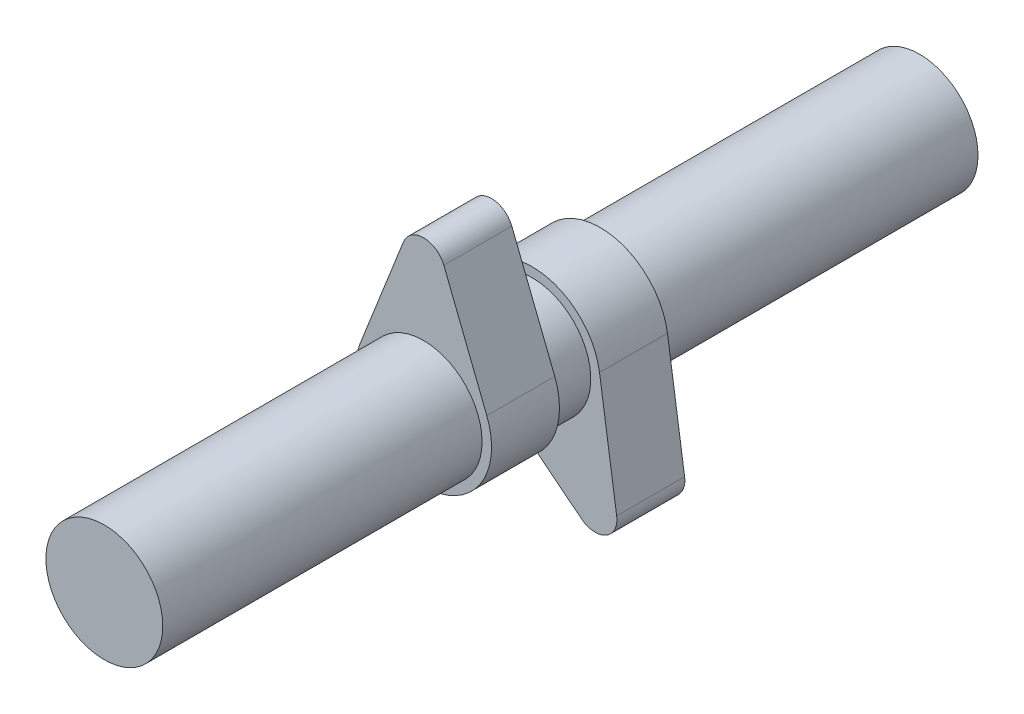
SolidWorks part; units mm, degrees
ref_plane "Front Plane" through (0, 0, 0) normal (0, 0, 1) x (1, 0, 0)
ref_plane "Top Plane" through (0, 0, 0) normal (0, 1, 0) x (1, 0, 0)
ref_plane "Right Plane" through (0, 0, 0) normal (1, 0, 0) x (0, 0, -1)
sketch "Sketch2" plane through (0, 0, 0) normal (0, 0, 1) x (1, 0, 0)
  circle A0 centre (0, 0) radius 21.5
  dimension "D1" = 43
extrude "Boss-Extrude1" add sketch "Sketch2" along normal mid plane 300 contours A0
sketch "Sketch3" plane through (0, 0, 150) normal (0, 0, 1) x (1, 0, 0)
  line L3 (-23.2498, 9.1894) -> (-7.4399, 49.1894)
  line L4 (7.4399, 49.1894) -> (23.2498, 9.1894)
  arc A1 (-7.4399, 49.1894) -> (7.4399, 49.1894) centre (0, 46.2488) cw
  arc A3 (-23.2498, 9.1894) -> (23.2498, 9.1894) centre (0, 0) ccw
  circle M6 centre (0, 0) radius 21.5
  dimension "D1" = 8
  dimension "D2" = 25
  dimension "D3" = 40
extrude "Boss-Extrude2" add sketch "Sketch3" against normal mid plane 25 from offset 130 contours A1 M6 region at (-14.4734, 28.845, 150) offset against normal yes
sketch "Sketch4" plane through (0, 0, 150) normal (0, 0, 1) x (1, 0, 0)
  line L0 (24.7297, 3.6666) -> (31.0379, -38.8793)
  line L1 (18.1515, -46.3193) -> (-15.5402, -19.5832)
  line L2 (-23.2498, 9.1894) -> (-7.4399, 49.1894) construction
  line L3 (7.4399, 49.1894) -> (23.2498, 9.1894) construction
  line L4 (0, 0) -> (0, -25) construction
  line L5 (23.1244, -40.0526) -> (27.1244, -46.9808) construction
  arc A0 (31.0379, -38.8793) -> (18.1515, -46.3193) centre (23.1244, -40.0526) cw
  arc A1 (24.7297, 3.6666) -> (-15.5402, -19.5832) centre (0, 0) ccw
  arc A3 (-23.2498, 9.1894) -> (23.2498, 9.1894) centre (0, 0) ccw construction
  arc A4 (7.4399, 49.1894) -> (-7.4399, 49.1894) centre (0, 46.2488) ccw construction
  dimension "D1" = 150
extrude "Boss-Extrude3" add sketch "Sketch4" along normal mid plane 25 from offset 170 offset against normal yes
equation "\"Camshaft Radius\"= 43mm'CHANGE LATER"
equation "\"Lobe Radius\" = 25mm'CHANGLE LATER"
equation "\"D1@Sketch2\"=\"Camshaft Radius\""
equation "\"D2@Sketch3\"=\"Lobe Radius\""
